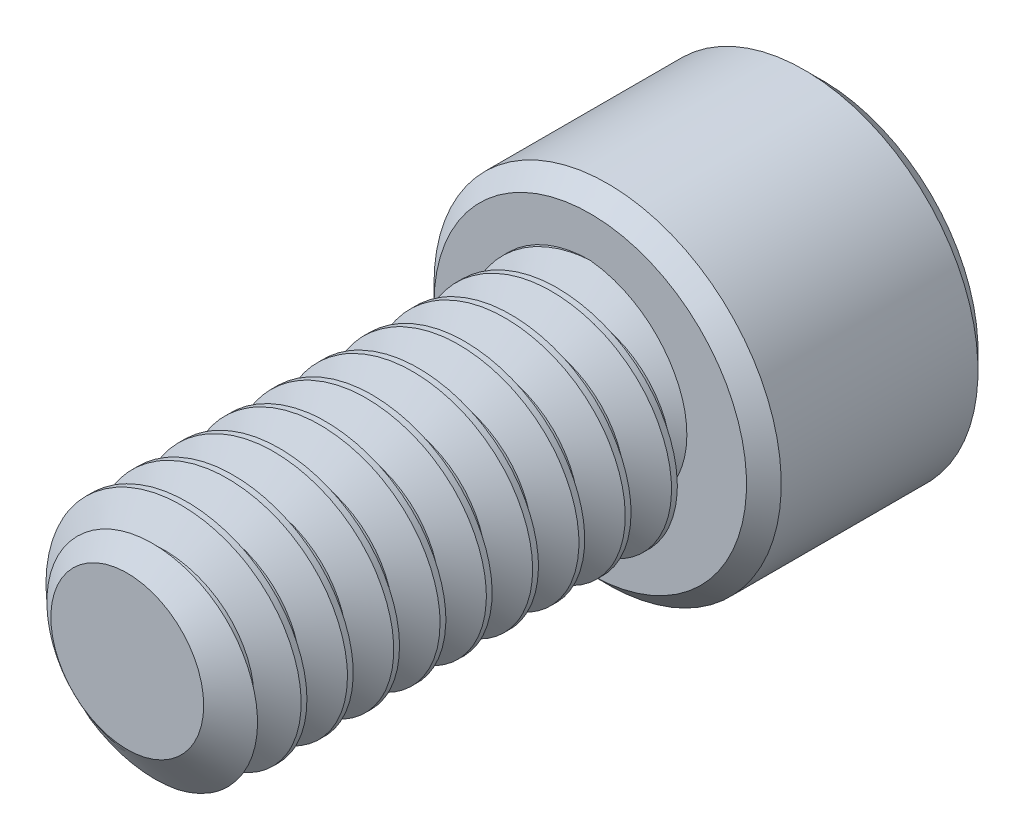
SolidWorks part; units mm, degrees
ref_plane "Front Plane" through (0, 0, 0) normal (0, 0, 1) x (1, 0, 0)
ref_plane "Top Plane" through (0, 0, 0) normal (0, 1, 0) x (1, 0, 0)
ref_plane "Right Plane" through (0, 0, 0) normal (1, 0, 0) x (0, 0, -1)
sketch "Sketch1" plane through (0, 0, 0) normal (0, 0, 1) x (1, 0, 0)
  circle A0 centre (0, 0) radius 3.175
  dimension "OD" = 6.35
extrude "Extrude1" add sketch "Sketch1" against normal blind 12.7
sketch "Sketch2" plane through (0, 0, 0) normal (0, 0, 1) x (1, 0, 0)
  circle A0 centre (0, 0) radius 3.175 construction
  circle A1 centre (0, 0) radius 3.175
curve "Helix/Spiral1" pitch 1.27 height 13.97 turns 11 parameters "pitch"=1.27
sketch "Sketch3" plane through (0, 0, 0) normal (1, 0, 0) x (0, 0, -1)
  line L0 (-1.1112, 3.175) -> (-0.635, 2.3501)
  line L1 (-0.635, 2.3501) -> (-0.4763, 2.3501)
  line L2 (-0.4763, 2.3501) -> (0, 3.175)
  line L3 (-1.1112, 3.175) -> (0, 3.175)
  line L4 (-0.5556, 3.175) -> (-0.5556, 2.3501) construction
  line L5 (-0.8731, 2.7626) -> (-0.2381, 2.7626) construction
  line L6 (0, 3.175) -> (0, -3.175) construction
  dimension "D1" = 0.1588
  dimension "D2" = 0.635
  dimension "D3" = 60
sweep "Cut-Sweep1" cut profiles "Sketch3" path "Helix/Spiral1"
sketch "Sketch4" plane through (0, 0, 0) normal (1, 0, 0) x (0, 0, -1)
  line L0 (0.7554, 3.175) -> (0, 2.0961)
  line L1 (0, 2.0961) -> (0, 3.175)
  line L2 (0.7554, 3.175) -> (0, 3.175)
  line L3 (-1.1112, 3.175) -> (0, 3.175) construction
  line L4 (0, 0) -> (7.0209, 0) construction
  dimension "D1" = 55
  dimension "D2" = 0.254
revolve "Cut-Revolve1" cut sketch "Sketch4" angle 360 about L4
sketch "Sketch5" plane through (0, 0, 0) normal (1, 0, 0) x (0, 0, -1)
  line L0 (12.7, -2.3728) -> (12.7, 2.2654) construction
  line L1 (12.7, 3.302) -> (87.4327, 3.302)
  line L2 (12.7, 3.302) -> (12.7, 0)
  line L3 (12.7, 0) -> (87.3125, 0)
  line L4 (87.3125, 2.9718) -> (87.3125, 0)
  line L5 (87.4327, 3.302) -> (87.3125, 2.9718)
  line L6 (0, 0) -> (9.9695, 0) construction
  point P3 (87.3125, 3.302)
  point P10 (87.3125, 3.302)
  dimension "D1" = 0.3302
  dimension "Thread min" = 87.3125
  dimension "D2" = 0.127
  dimension "D3" = 20
revolve "partially thread" [suppressed] add sketch "Sketch5" angle 360 about L6
sketch "Sketch6" plane through (0, 0, -12.7) normal (0, 0, -1) x (-1, 0, 0)
  circle A0 centre (0, 0) radius 4.7625
  dimension "head dia" = 9.525
extrude "Extrude2" add sketch "Sketch6" along normal blind 6.35
sketch "Sketch7" plane through (0, 0, -19.05) normal (0, 0, -1) x (-1, 0, 0)
  line L1 (0, 2.7496) -> (-2.3813, 1.3748)
  line L2 (-2.3813, 1.3748) -> (-2.3813, -1.3748)
  line L3 (-2.3813, -1.3748) -> (0, -2.7496)
  line L4 (0, -2.7496) -> (2.3813, -1.3748)
  line L5 (2.3813, -1.3748) -> (2.3813, 1.3748)
  line L6 (2.3813, 1.3748) -> (0, 2.7496)
  circle A0 centre (0, 0) radius 2.3813 construction
  dimension "hex dia" = 4.7625
extrude "Cut-Extrude1" cut sketch "Sketch7" against normal blind 3.5719
sketch "Sketch8" plane through (0, 0, -19.05) normal (0, 0, -1) x (-1, 0, 0)
  circle A0 centre (0, 0) radius 2.7496
extrude "Cut-Extrude2" cut sketch "Sketch8" against normal through all draft 45
chamfer "Chamfer1" distance 0.4763 angle 45 2 edges at (-4.7625, 0, -19.05) (-4.7625, 0, -12.7)
sketch "Sketch9" plane through (0, 0, 0) normal (1, 0, 0) x (0, 0, -1)
  line L0 (0, 3.175) -> (0, -3.175) construction
  line L1 (6.985, 3.175) -> (6.985, -3.175) construction
  dimension "D1" = 6.985
equation "\"D3@Helix/Spiral1\" = \"screw length@Extrude1\"+\"pitch@Helix/Spiral1\""
equation "\"D1@Sketch3\" = \"pitch@Helix/Spiral1\"*.125"
equation "\"D2@Sketch3\" = \"pitch@Helix/Spiral1\"*.5"
equation "\"D1@Cut-Extrude1\" = \"hex dia@Sketch7\"*.75"
equation "\"D1@Chamfer1\" = \"head dia@Sketch6\"*.05"
equation "\"D1@Sketch9\" = \"pitch@Helix/Spiral1\"*5.5"
